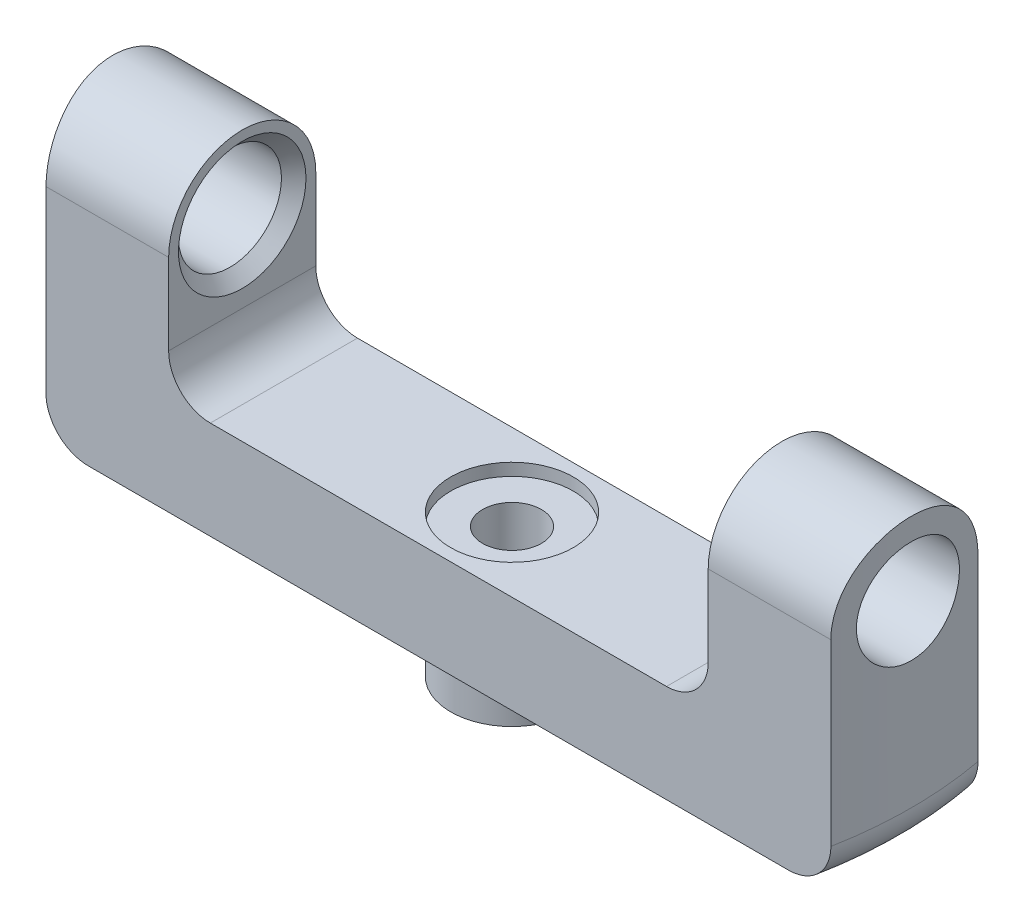
SolidWorks part; units mm, degrees
ref_plane "Front Plane" through (0, 0, 0) normal (0, 0, 1) x (1, 0, 0)
ref_plane "Top Plane" through (0, 0, 0) normal (0, 1, 0) x (1, 0, 0)
ref_plane "Right Plane" through (0, 0, 0) normal (1, 0, 0) x (0, 0, -1)
sketch "Sketch1" plane through (0, 0, 0) normal (0, 1, 0) x (1, 0, 0)
  line L1 (16, 3) -> (-16, 3)
  line L2 (16, 3) -> (16, -3)
  line L3 (16, -3) -> (-16, -3)
  line L4 (-16, 3) -> (-16, -3)
  line L5 (11, -3) -> (-11, -3)
  line L6 (11, -3) -> (11, 3)
  line L7 (11, 3) -> (-11, 3)
  line L8 (-11, -3) -> (-11, 3)
  line L9 (0, 3) -> (0, -3) construction
  line L10 (11, 0) -> (-11, 0) construction
  circle A0 centre (0, 0) radius 16.2788
  dimension "D1" = 5
  dimension "D2" = 6
  dimension "D3" = 22
extrude "Boss-Extrude1" add sketch "Sketch1" along normal blind 4 contours L3 L8 L1 L4 | L8 L3 L6 L1 | L6 L3 L2 L1 | L4 A0 | L2 A0 region at (13.5, 0, 0) region at (16.1116, 0, 0) region at (0, 0, 0) region at (-13.5, 0, 0) region at (-16.1116, 0, 0)
extrude "Boss-Extrude2" add sketch "Sketch1<3>" along normal blind 8 from surface contours L3 L8 L1 L4 | L4 A0 | L6 L3 L2 L1 | L2 A0 region at (13.5, 0, 0) region at (16.1116, 0, 0) region at (-13.5, 0, 0) region at (-16.1116, 0, 0) starting at face at (0, 4, 0)
sketch "Sketch1<3>" plane through (0, 0, 0) normal (0, 1, 0) x (1, 0, 0) same geometry as "Sketch1"
sketch "Sketch2" plane through (-11, 0, 0) normal (1, 0, 0) x (0, 0, -1)
  line L2 (3, 12) -> (-3, 12) construction
  line L4 (-3, 12) -> (-3, 4) construction
  line L5 (3, 12) -> (3, 4) construction
  circle A0 centre (0, 9) radius 2.1
  arc A1 (-3, 9) -> (3, 9) centre (0, 9) cw
  line M2 (3, 4) -> (3, 12)
  line M3 (3, 12) -> (-3, 12)
  line M4 (-3, 12) -> (-3, 4)
  dimension "D1" = 4.2
extrude "Cut-Extrude1" cut sketch "Sketch2" against normal through all both and the other way through all contours A1 M3 M2 | A1 M4 M3 | A0 region at (-11, 9, 0) region at (-11, 11.3299, 2.3299) region at (-11, 11.3299, -2.3299)
sketch "Sketch4" plane through (0, 0, 0) normal (0, -1, 0) x (1, 0, 0)
  circle A0 centre (0, 0) radius 2.5
  dimension "D1" = 5
extrude "Boss-Extrude3" add sketch "Sketch4" along normal blind 1.8
sketch "Sketch5" plane through (0, -1.8, 0) normal (0, -1, 0) x (1, 0, 0)
  circle A0 centre (0, 0) radius 1.2
  dimension "D1" = 2.4
extrude "Cut-Extrude2" cut sketch "Sketch5" against normal through all both and the other way through all
sketch "Sketch6" plane through (0, 4, 0) normal (0, 1, 0) x (1, 0, 0)
  circle A0 centre (0, 0) radius 2.5
  dimension "D1" = 5
extrude "Cut-Extrude3" cut sketch "Sketch6" against normal blind 0.5
chamfer "Chamfer1" distance 0.5 angle 45 2 edges at (11, 9, -2.1) (-11, 9, -2.1)
fillet "Fillet1" radius 1.7 4 edges at (16.2788, 0, 0) (-16.2788, 0, 0) (-11, 4, 0) (11, 4, 0)
equation "\"bandwidth\"= 20mm"
equation "\"loosefit\"= 0.5mm"
equation "\"tightfit\"= 0.2mm"
equation "\"D3@Sketch1\"=\"bandwidth\" + 4*\"loosefit\""
